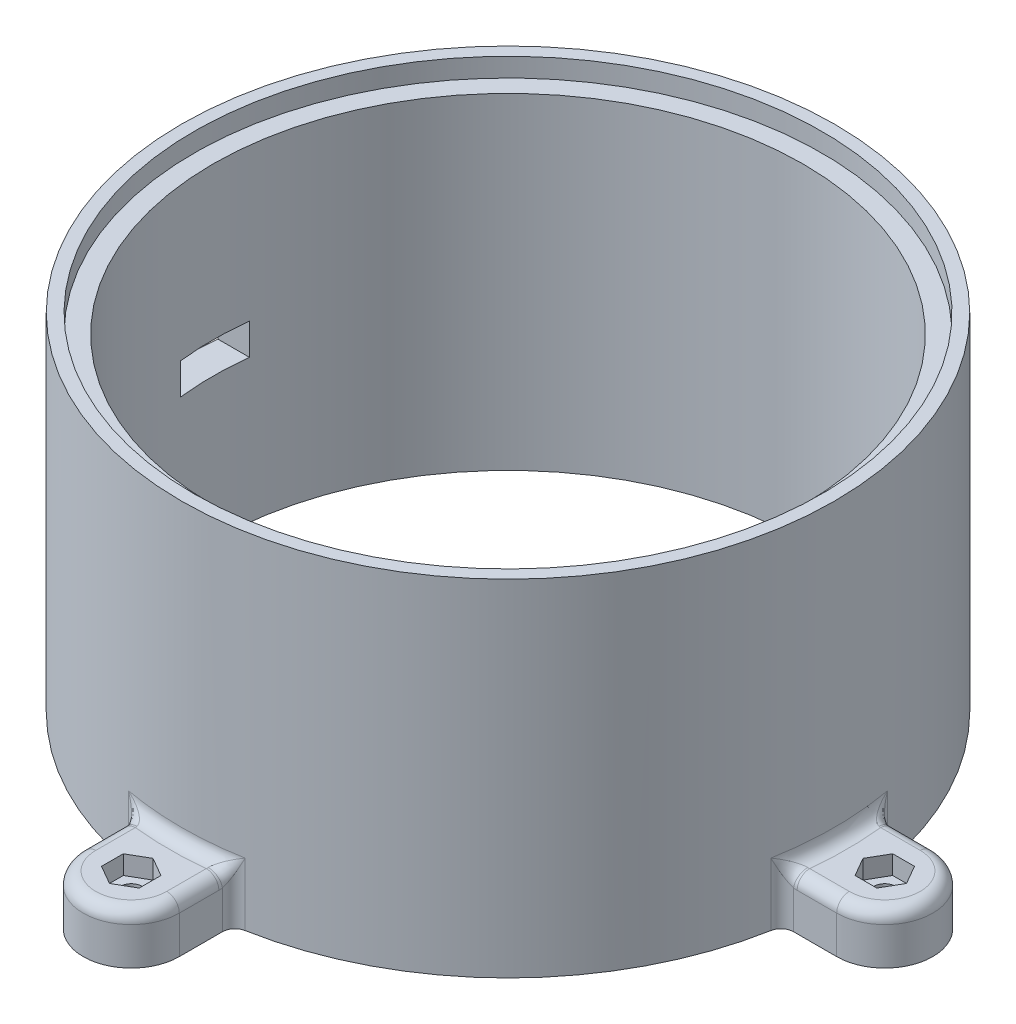
SolidWorks part; units mm, degrees
ref_plane "Front" through (0, 0, 0) normal (0, 0, 1) x (1, 0, 0)
ref_plane "Top" through (0, 0, 0) normal (0, 1, 0) x (1, 0, 0)
ref_plane "Right" through (0, 0, 0) normal (1, 0, 0) x (0, 0, -1)
sketch "Эскиз1" plane through (0, 0, 0) normal (0, 0, 1) x (1, 0, 0)
  line L0 (0, 69.6444) -> (0, 0) construction
  line L1 (-50, 55) -> (-50, 52)
  line L2 (-50, 52) -> (-47, 52)
  line L3 (-47, 52) -> (-47, 0)
  line L4 (-47, 3) -> (0, 3)
  line L5 (0, 3) -> (0, 0)
  line L6 (0, 0) -> (-52, 0)
  line L7 (-52, 0) -> (-52, 55)
  line L8 (-52, 55) -> (-50, 55)
  dimension "D1" = 50
  dimension "D2" = 3
  dimension "D3" = 3
  dimension "D4" = 3
  dimension "D5" = 2
  dimension "D6" = 55
revolve "Повернуть1" add sketch "Эскиз1" angle 360 about L0 region at (-49.5338, 26.6203, 0)
sketch "Эскиз3" plane through (0, 0, 0) normal (0, -1, 0) x (1, 0, 0)
  line L0 (0, 0) -> (-60, 0) construction
  line L1 (-51.4338, 7.6526) -> (-60, 7.6526)
  line L2 (-51.4338, 7.6526) -> (-51.4338, -7.6526)
  line L3 (-51.4338, -7.6526) -> (-60, -7.6526)
  line L4 (-60, 7.6526) -> (-60, -7.6526)
  line L5 (25.5343, 0) -> (-25.5343, 0) construction
  circle A0 centre (0, 0) radius 52 construction
  arc A1 (-60, 7.6526) -> (-60, -7.6526) centre (-60, 0) ccw
  circle A2 centre (-60, 0) radius 1.75
  circle M5 centre (0, 0) radius 52
  dimension "D2" = 3.5
  dimension "D1" = 60
extrude "Бобышка-Вытянуть2" add sketch "Эскиз3" against normal blind 8 contours A2 L4 A1 | L0 A2 L4 L3 M5 | L0 L1 L4 A2 M5 region at (-55.7703, 0, 3.9952) region at (-55.7703, 0, -3.9952) region at (-63.3861, 0, 0)
fillet "Скругление1" radius 2 3 edges at (-51.4338, 4, -7.6526) (-51.4338, 4, 7.6526) (-52, 8, 0)
fillet "Скругление2" radius 2 7 edges at (-52.097, 8.4813, 7.9402) (-56.7275, 8, 7.6526) (-52.097, 8.4813, -7.9402) (-56.7275, 8, -7.6526) (-67.6526, 8, 0)
sketch "Эскиз4" plane through (0, 8, 0) normal (0, 1, 0) x (1, 0, 0)
  line L1 (-63.4641, 0) -> (-61.7321, -3)
  line L2 (-61.7321, -3) -> (-58.2679, -3)
  line L3 (-58.2679, -3) -> (-56.5359, 0)
  line L4 (-56.5359, 0) -> (-58.2679, 3)
  line L5 (-58.2679, 3) -> (-61.7321, 3)
  line L6 (-61.7321, 3) -> (-63.4641, 0)
  circle A0 centre (-60, 0) radius 1.75 construction
  circle A1 centre (-60, 0) radius 1.75
  circle A2 centre (-60, 0) radius 3 construction
  dimension "D1" = 6
extrude "Вырез-Вытянуть1" cut sketch "Эскиз4" against normal blind 3
pattern_circular "Круговой массив1" count 4 every 90 about axis through (0, 69.6444, 0) along (0, 1, 0) of "Бобышка-Вытянуть2", "Скругление2", "Скругление1", "Вырез-Вытянуть1"
sketch "Эскиз5" plane through (0, 0, 0) normal (1, 0, 0) x (0, 0, -1)
  line L0 (0, 0) -> (0, 48.7324) construction
  line L2 (5.5, 27.7451) -> (-5.5, 27.7451)
  line L3 (5.5, 27.7451) -> (5.5, 22.7451)
  line L4 (5.5, 22.7451) -> (-5.5, 22.7451)
  line L5 (-5.5, 27.7451) -> (-5.5, 22.7451)
  dimension "D1" = 11
  dimension "D2" = 5
extrude "Вырез-Вытянуть2" cut sketch "Эскиз5" against normal through all
